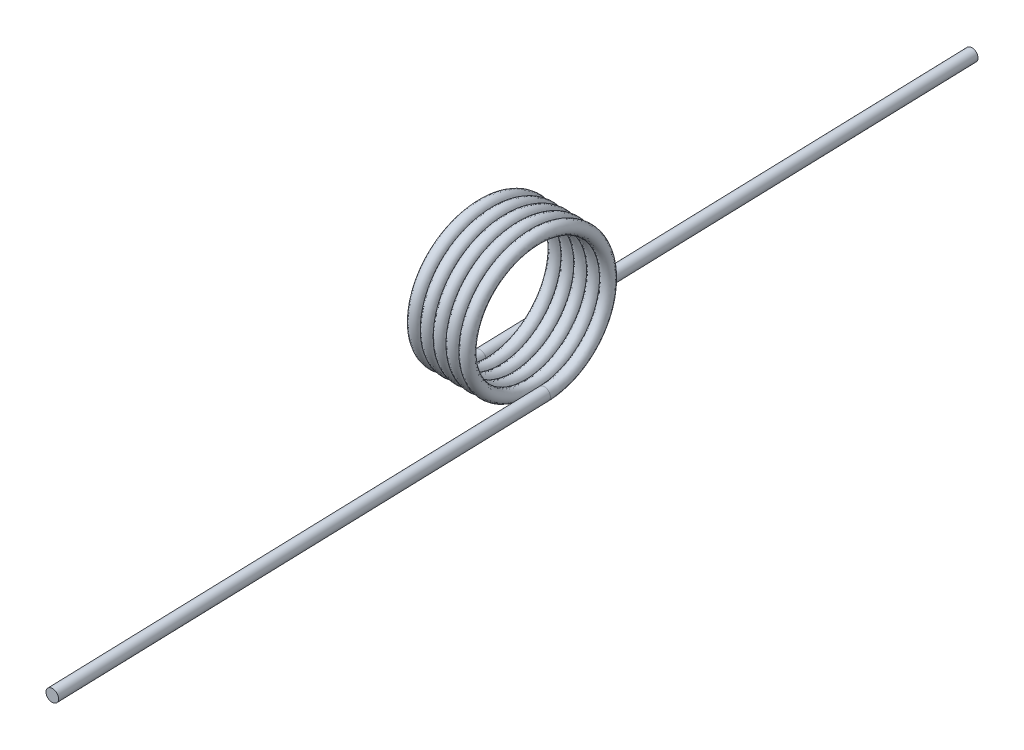
SolidWorks part; units mm, degrees
ref_plane "Front" through (0, 0, 0) normal (0, 0, 1) x (1, 0, 0)
ref_plane "Top" through (0, 0, 0) normal (0, 1, 0) x (1, 0, 0)
ref_plane "Right" through (0, 0, 0) normal (1, 0, 0) x (0, 0, -1)
sketch "Sketch1" plane through (0, 0, 0) normal (1, 0, 0) x (0, 0, -1)
  line L0 (0, 0) -> (0, -2.286) construction
  line L1 (0, -2.286) -> (0, -2.5146) construction
  line L2 (0, -2.5146) -> (0, -2.7432) construction
  circle A0 centre (0, 0) radius 2.286 construction
  circle A1 centre (0, 0) radius 2.7432 construction
  circle A2 centre (0, 0) radius 2.5146
  circle A3 centre (0, -2.5146) radius 0.2286 construction
  circle A4 centre (0, 0) radius 1.778 construction
  dimension "Wire Dia" = 0.4572
  dimension "Spring OD" = 5.4864
  dimension "Max Rod OD" = 3.556
curve "Helix/Spiral1" pitch 0.4826 height 2.413 turns 5
ref_plane "Plane1" through (0, -2.5146, 0) normal (0.0305, 0, 0.9995) x (0.9995, 0, -0.0305)
sketch "Sketch2" plane through (0, -2.5146, 0) normal (0.0305, 0, 0.9995) x (0.9995, 0, -0.0305)
  circle A0 centre (0, 0) radius 0.2286
  dimension "D1" = 0.4572
sweep "Sweep1" add profiles "Sketch2" path "Helix/Spiral1"
sketch "Sketch3" plane through (0, 0, 0) normal (-0.0305, 0, -0.9995) x (-0.9995, 0, 0.0305)
  circle A1 centre (0, -2.5146) radius 0.2286
  circle A2 centre (0, -2.5146) radius 0.2286
  dimension "D1" = 0
extrude "Extrude1" add sketch "Sketch3" along normal blind 19.05
sketch "Sketch4" plane through (0.0022, 0, 0.0736) normal (0.0305, 0, 0.9995) x (0.9959, -0.0856, -0.0304)
  circle A1 centre (2.6183, -2.2989) radius 0.2286
  circle A2 centre (2.6183, -2.2989) radius 0.2286
  dimension "D1" = 0
extrude "Extrude2" add sketch "Sketch4" along normal blind 19.05
sketch "Sketch5" plane through (0, 0, 0) normal (1, 0, 0) x (0, 0, -1)
  circle A0 centre (0, 0) radius 1.778 construction
  circle A1 centre (0, 0) radius 1.778
equation "\"D4@Helix/Spiral1\"=\"Wire Dia@Sketch1\"+.001"
equation "\"D1@Sketch2\"=\"Wire Dia@Sketch1\""
equation "\"D1@Extrude2\"=\"Leg Length@Extrude1\""
